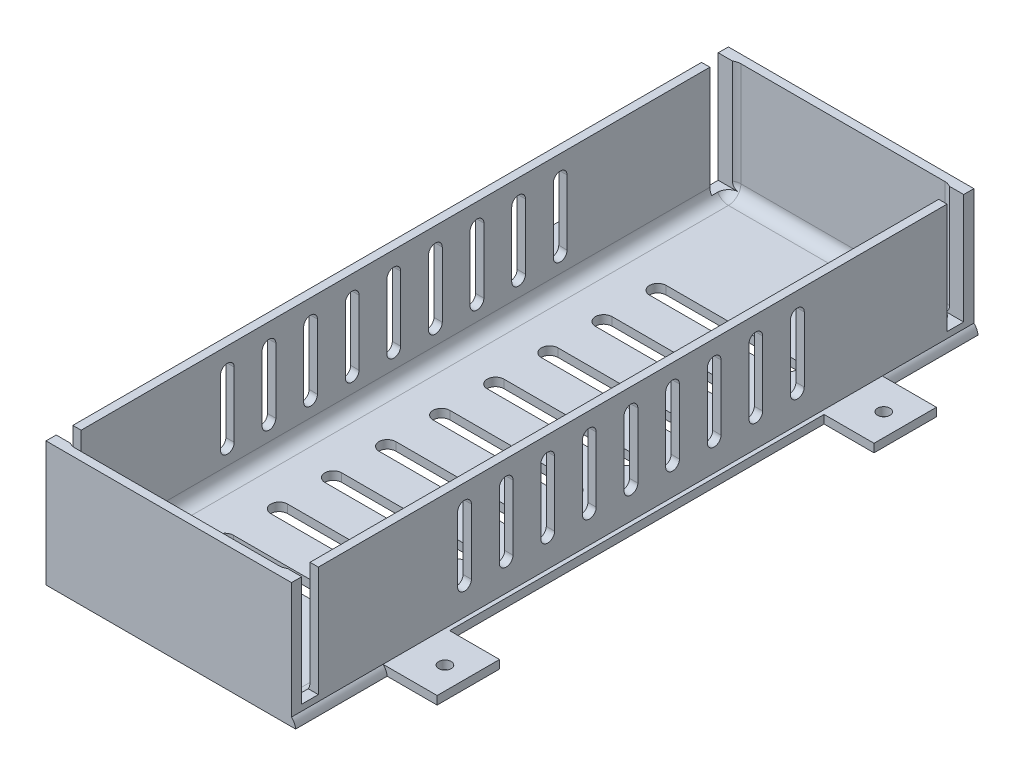
SolidWorks part; units mm, degrees
ref_plane "Front Plane" through (0, 0, 0) normal (0, 0, 1) x (1, 0, 0)
ref_plane "Top Plane" through (0, 0, 0) normal (0, 1, 0) x (1, 0, 0)
ref_plane "Right Plane" through (0, 0, 0) normal (1, 0, 0) x (0, 0, -1)
sketch "Sketch1" plane through (0, 0, 0) normal (0, 1, 0) x (1, 0, 0)
  line L1 (-30, 82) -> (30, 82)
  line L2 (-30, 82) -> (-30, -82)
  line L3 (-30, -82) -> (30, -82)
  line L4 (30, 82) -> (30, -82)
  line L5 (-30, 82) -> (30, -82) construction
  line L6 (-30, -82) -> (30, 82) construction
  point P0 (0, 0)
  dimension "D1" = 164
  dimension "D2" = 60
extrude "Boss-Extrude1" add sketch "Sketch1" along normal blind 2
sketch "Sketch2" plane through (0, 2, 0) normal (0, 1, 0) x (1, 0, 0)
  line L0 (30, 82) -> (-30, 82) construction
  line L1 (-30, 82) -> (29, 82)
  line L2 (-30, 82) -> (-30, -82)
  line L3 (-30, -82) -> (29, -82)
  line L4 (29, 82) -> (29, -82)
  line L5 (-30, 82) -> (29, -82) construction
  line L6 (-30, -82) -> (29, 82) construction
  line L7 (-30, 82) -> (-30, -82) construction
  line L9 (-28, 80) -> (27, 80)
  line L10 (-28, 80) -> (-28, -80)
  line L11 (-28, -80) -> (27, -80)
  line L12 (27, 80) -> (27, -80)
  line L13 (-28, 80) -> (27, -80) construction
  line L14 (-28, -80) -> (27, 80) construction
  point P4 (-0.5, 0)
  point P9 (-0.5, 0)
  dimension "D1" = 164
  dimension "D2" = 59
  dimension "D3" = 160
  dimension "D4" = 55
extrude "Boss-Extrude2" add sketch "Sketch2" along normal blind 28
sketch "Sketch5" plane through (30, 0, 0) normal (1, 0, 0) x (0, 0, -1)
  line L0 (0, 41.9925) -> (0, -40.4954) construction
  line L1 (-82, 0) -> (82, 0) construction
  line L2 (45, 2) -> (60, 2)
  line L3 (45, 2) -> (45, 0)
  line L4 (45, 0) -> (60, 0)
  line L5 (60, 2) -> (60, 0)
  line L6 (45, 2) -> (60, 0) construction
  line L7 (45, 0) -> (60, 2) construction
  point P3 (52.5, 1)
  point P10 (45, 1)
  dimension "D1" = 2
  dimension "D2" = 15
  dimension "D3" = 45
extrude "Boss-Extrude5" add sketch "Sketch5" along normal blind 12
fillet "Fillet3" radius 3 4 edges at (-28, 16, 80) (27, 16, 80) (27, 16, -80) (-28, 16, -80)
fillet "Fillet4" radius 3 8 edges at (-27.1213, 2, 79.1213) (-28, 2, 0) (-27.1213, 2, -79.1213) (-0.5, 2, -80) (26.1213, 2, -79.1213) (27, 2, 0) (26.1213, 2, 79.1213) (-0.5, 2, 80)
mirror "Mirror1" about plane through (0, 0, 0) normal (0, 0, 1) of "Boss-Extrude5"
mirror "Mirror2" about plane through (0, 0, 0) normal (1, 0, 0) of "Boss-Extrude5", "Mirror1"
fillet "Fillet6" radius 3 12 edges at (30, 1, 60) (-30, 2, -52.5) (-30, 2, 52.5) (29.5, 2, 82) (30, 0, -71) (30, 2, -71) (30, 1, -60) (30, 2, 71) (30, 0, 71) (29.5, 2, -82) (30, 1, 82) (30, 1, -82)
sketch "Sketch11" plane through (-30, 0, 0) normal (-1, 0, 0) x (0, 0, 1)
  line L0 (-39.5845, 24.7206) -> (-39.5845, 9.0857) construction
  line L1 (-37.9338, 24.7206) -> (-37.9338, 9.0857)
  line L2 (-41.2353, 24.7206) -> (-41.2353, 9.0857)
  line L3 (-29.5845, 24.7206) -> (-29.5845, 9.0857) construction
  line L4 (-27.9338, 24.7206) -> (-27.9338, 9.0857)
  line L5 (-31.2353, 24.7206) -> (-31.2353, 9.0857)
  line L6 (-19.5845, 24.7206) -> (-19.5845, 9.0857) construction
  line L7 (-17.9338, 24.7206) -> (-17.9338, 9.0857)
  line L8 (-21.2353, 24.7206) -> (-21.2353, 9.0857)
  line L9 (-9.5845, 24.7206) -> (-9.5845, 9.0857) construction
  line L10 (-7.9338, 24.7206) -> (-7.9338, 9.0857)
  line L11 (-11.2353, 24.7206) -> (-11.2353, 9.0857)
  line L12 (0.4155, 24.7206) -> (0.4155, 9.0857) construction
  line L13 (2.0662, 24.7206) -> (2.0662, 9.0857)
  line L14 (-1.2353, 24.7206) -> (-1.2353, 9.0857)
  line L15 (10.4155, 24.7206) -> (10.4155, 9.0857) construction
  line L16 (12.0662, 24.7206) -> (12.0662, 9.0857)
  line L17 (8.7647, 24.7206) -> (8.7647, 9.0857)
  line L18 (20.4155, 24.7206) -> (20.4155, 9.0857) construction
  line L19 (22.0662, 24.7206) -> (22.0662, 9.0857)
  line L20 (18.7647, 24.7206) -> (18.7647, 9.0857)
  line L21 (30.4155, 24.7206) -> (30.4155, 9.0857) construction
  line L22 (32.0662, 24.7206) -> (32.0662, 9.0857)
  line L23 (28.7647, 24.7206) -> (28.7647, 9.0857)
  line L24 (40.4155, 24.7206) -> (40.4155, 9.0857) construction
  line L25 (42.0662, 24.7206) -> (42.0662, 9.0857)
  line L26 (38.7647, 24.7206) -> (38.7647, 9.0857)
  arc A0 (-37.9338, 24.7206) -> (-41.2353, 24.7206) centre (-39.5845, 24.7206) ccw
  arc A1 (-41.2353, 9.0857) -> (-37.9338, 9.0857) centre (-39.5845, 9.0857) ccw
  arc A2 (-27.9338, 24.7206) -> (-31.2353, 24.7206) centre (-29.5845, 24.7206) ccw
  arc A3 (-31.2353, 9.0857) -> (-27.9338, 9.0857) centre (-29.5845, 9.0857) ccw
  arc A4 (-17.9338, 24.7206) -> (-21.2353, 24.7206) centre (-19.5845, 24.7206) ccw
  arc A5 (-21.2353, 9.0857) -> (-17.9338, 9.0857) centre (-19.5845, 9.0857) ccw
  arc A6 (-7.9338, 24.7206) -> (-11.2353, 24.7206) centre (-9.5845, 24.7206) ccw
  arc A7 (-11.2353, 9.0857) -> (-7.9338, 9.0857) centre (-9.5845, 9.0857) ccw
  arc A8 (2.0662, 24.7206) -> (-1.2353, 24.7206) centre (0.4155, 24.7206) ccw
  arc A9 (-1.2353, 9.0857) -> (2.0662, 9.0857) centre (0.4155, 9.0857) ccw
  arc A10 (12.0662, 24.7206) -> (8.7647, 24.7206) centre (10.4155, 24.7206) ccw
  arc A11 (8.7647, 9.0857) -> (12.0662, 9.0857) centre (10.4155, 9.0857) ccw
  arc A12 (22.0662, 24.7206) -> (18.7647, 24.7206) centre (20.4155, 24.7206) ccw
  arc A13 (18.7647, 9.0857) -> (22.0662, 9.0857) centre (20.4155, 9.0857) ccw
  arc A14 (32.0662, 24.7206) -> (28.7647, 24.7206) centre (30.4155, 24.7206) ccw
  arc A15 (28.7647, 9.0857) -> (32.0662, 9.0857) centre (30.4155, 9.0857) ccw
  arc A16 (42.0662, 24.7206) -> (38.7647, 24.7206) centre (40.4155, 24.7206) ccw
  arc A17 (38.7647, 9.0857) -> (42.0662, 9.0857) centre (40.4155, 9.0857) ccw
  point P2 (-39.5845, 16.9031)
  point P10 (-29.5845, 16.9031)
  point P18 (-19.5845, 16.9031)
  point P25 (-9.5845, 16.9031)
  point P32 (0.4155, 16.9031)
  point P39 (10.4155, 16.9031)
  point P46 (20.4155, 16.9031)
  point P53 (30.4155, 16.9031)
  point P60 (40.4155, 16.9031)
  dimension "D1" = 9
extrude "Cut-Extrude6" cut sketch "Sketch11" against normal up to surface (59 mm away) up to face at (29, 11.3333, 0)
sketch "Sketch12" plane through (0, 2, 0) normal (0, 1, 0) x (1, 0, 0)
  line L0 (-15.828, 50.8712) -> (15.3533, 50.8712) construction
  line L1 (-15.828, 52.8879) -> (15.3533, 52.8879)
  line L2 (-15.828, 48.8545) -> (15.3533, 48.8545)
  line L3 (-15.828, 37.8712) -> (15.3533, 37.8712) construction
  line L4 (-15.828, 39.8879) -> (15.3533, 39.8879)
  line L5 (-15.828, 35.8545) -> (15.3533, 35.8545)
  line L6 (-15.828, 24.8712) -> (15.3533, 24.8712) construction
  line L7 (-15.828, 26.8879) -> (15.3533, 26.8879)
  line L8 (-15.828, 22.8545) -> (15.3533, 22.8545)
  line L9 (-15.828, 11.8712) -> (15.3533, 11.8712) construction
  line L10 (-15.828, 13.8879) -> (15.3533, 13.8879)
  line L11 (-15.828, 9.8545) -> (15.3533, 9.8545)
  line L12 (-15.828, -1.1288) -> (15.3533, -1.1288) construction
  line L13 (-15.828, 0.8879) -> (15.3533, 0.8879)
  line L14 (-15.828, -3.1455) -> (15.3533, -3.1455)
  line L15 (-15.828, -14.1288) -> (15.3533, -14.1288) construction
  line L16 (-15.828, -12.1121) -> (15.3533, -12.1121)
  line L17 (-15.828, -16.1455) -> (15.3533, -16.1455)
  line L18 (-15.828, -27.1288) -> (15.3533, -27.1288) construction
  line L19 (-15.828, -25.1121) -> (15.3533, -25.1121)
  line L20 (-15.828, -29.1455) -> (15.3533, -29.1455)
  line L21 (-15.828, -40.1288) -> (15.3533, -40.1288) construction
  line L22 (-15.828, -38.1121) -> (15.3533, -38.1121)
  line L23 (-15.828, -42.1455) -> (15.3533, -42.1455)
  line L24 (-15.828, -53.1288) -> (15.3533, -53.1288) construction
  line L25 (-15.828, -51.1121) -> (15.3533, -51.1121)
  line L26 (-15.828, -55.1455) -> (15.3533, -55.1455)
  arc A0 (-15.828, 52.8879) -> (-15.828, 48.8545) centre (-15.828, 50.8712) ccw
  arc A1 (15.3533, 48.8545) -> (15.3533, 52.8879) centre (15.3533, 50.8712) ccw
  arc A2 (-15.828, 39.8879) -> (-15.828, 35.8545) centre (-15.828, 37.8712) ccw
  arc A3 (15.3533, 35.8545) -> (15.3533, 39.8879) centre (15.3533, 37.8712) ccw
  arc A4 (-15.828, 26.8879) -> (-15.828, 22.8545) centre (-15.828, 24.8712) ccw
  arc A5 (15.3533, 22.8545) -> (15.3533, 26.8879) centre (15.3533, 24.8712) ccw
  arc A6 (-15.828, 13.8879) -> (-15.828, 9.8545) centre (-15.828, 11.8712) ccw
  arc A7 (15.3533, 9.8545) -> (15.3533, 13.8879) centre (15.3533, 11.8712) ccw
  arc A8 (-15.828, 0.8879) -> (-15.828, -3.1455) centre (-15.828, -1.1288) ccw
  arc A9 (15.3533, -3.1455) -> (15.3533, 0.8879) centre (15.3533, -1.1288) ccw
  arc A10 (-15.828, -12.1121) -> (-15.828, -16.1455) centre (-15.828, -14.1288) ccw
  arc A11 (15.3533, -16.1455) -> (15.3533, -12.1121) centre (15.3533, -14.1288) ccw
  arc A12 (-15.828, -25.1121) -> (-15.828, -29.1455) centre (-15.828, -27.1288) ccw
  arc A13 (15.3533, -29.1455) -> (15.3533, -25.1121) centre (15.3533, -27.1288) ccw
  arc A14 (-15.828, -38.1121) -> (-15.828, -42.1455) centre (-15.828, -40.1288) ccw
  arc A15 (15.3533, -42.1455) -> (15.3533, -38.1121) centre (15.3533, -40.1288) ccw
  arc A16 (-15.828, -51.1121) -> (-15.828, -55.1455) centre (-15.828, -53.1288) ccw
  arc A17 (15.3533, -55.1455) -> (15.3533, -51.1121) centre (15.3533, -53.1288) ccw
  point P2 (-0.2373, 50.8712)
  point P10 (-0.2373, 37.8712)
  point P17 (-0.2373, 24.8712)
  point P24 (-0.2373, 11.8712)
  point P31 (-0.2373, -1.1288)
  point P38 (-0.2373, -14.1288)
  point P45 (-0.2373, -27.1288)
  point P52 (-0.2373, -40.1288)
  point P59 (-0.2373, -53.1288)
  dimension "D1" = 9
extrude "Cut-Extrude7" cut sketch "Sketch12" against normal up to surface (2 mm away) up to face at (-0.0019, 0, 0)
sketch "Sketch13" plane through (29, 0, 0) normal (1, 0, 0) x (0, 0, -1)
  line L0 (-82, 30) -> (82, 30) construction
  line L1 (-79.5501, 30) -> (-75.5501, 30)
  line L2 (-79.5501, 30) -> (-79.5501, 3.4662)
  line L3 (-79.5501, 3.4662) -> (-75.5501, 3.4662)
  line L4 (-75.5501, 30) -> (-75.5501, 3.4662)
  line L5 (-79.5501, 30) -> (-75.5501, 3.4662) construction
  line L6 (-79.5501, 3.4662) -> (-75.5501, 30) construction
  point P4 (-77.5501, 16.7331)
  dimension "D1" = 26.5338
  dimension "D2" = 4
extrude "Cut-Extrude8" cut sketch "Sketch13" against normal up to surface (59 mm away)
mirror "Mirror3" about plane through (0, 0, 0) normal (0, 0, 1) of "Cut-Extrude8"
sketch "Sketch14" plane through (0, 2, 0) normal (0, 1, 0) x (1, 0, 0)
  circle A0 centre (36.6053, -52.7263) radius 1.5
extrude "Cut-Extrude9" cut sketch "Sketch14" against normal up to surface (2 mm away) up to face at (-0.2373, 0, -37.8712)
mirror "Mirror4" about plane through (0, 0, 0) normal (0, 0, 1) of "Cut-Extrude9"
mirror "Mirror5" about plane through (0, 0, 0) normal (1, 0, 0) of "Mirror4", "Cut-Extrude9"
